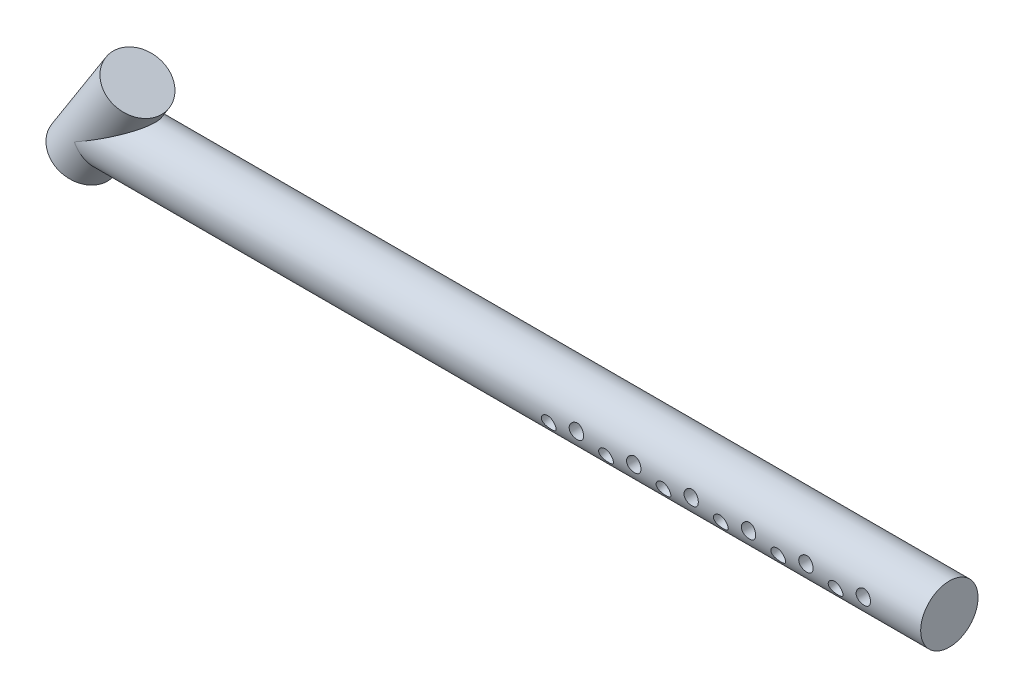
SolidWorks part; units mm, degrees
ref_plane "Front Plane" through (0, 0, 0) normal (0, 0, 1) x (1, 0, 0)
ref_plane "Top Plane" through (0, 0, 0) normal (0, 1, 0) x (1, 0, 0)
ref_plane "Right Plane" through (0, 0, 0) normal (1, 0, 0) x (0, 0, -1)
sketch "Sketch1" plane through (0, 0, 0) normal (0, 0, 1) x (1, 0, 0)
  line L0 (0, 0) -> (-374.65, 0)
  line L1 (211.1174, 0) -> (-211.1174, 0) construction
  line L2 (-359.3649, 23.9928) -> (-383.2479, -13.4959)
  point P7 (-25.4, 0)
  point P8 (-38.1, 0)
  dimension "D1" = 122.5
  dimension "D2" = 44.45
  dimension "D3" = 374.65
  dimension "D4" = 25.4
  dimension "D5" = 12.7
  dimension "D6" = 28.448
sweep "Sweep1" add path "Sketch1" circular profile diameter 25.4 parameters "D3"=25.4
sweep "Sweep2" add path "Sketch1<3>" circular profile diameter 25.4 parameters "D3"=25.4
sketch "Sketch1<3>" plane through (0, 0, 0) normal (0, 0, 1) x (1, 0, 0) same geometry as "Sketch1"
sketch "Sketch18" plane through (0, 0, 0) normal (0, 0, 1) x (1, 0, 0)
  circle A0 centre (-25.4, 0) radius 3.175
  dimension "D1" = 6.35
extrude "Cut-Extrude1" cut sketch "Sketch18" against normal through all both and the other way through all
ref_plane "Plane1" through (0, 0, 0) normal (0, -0.2588, 0.9659) x (-1, 0, 0)
sketch "Sketch23" plane through (0, 0, 0) normal (0, -0.2588, 0.9659) x (-1, 0, 0)
  circle A0 centre (38.1, 0) radius 3.175
  dimension "D1" = 6.35
extrude "Cut-Extrude2" cut sketch "Sketch23" against normal through all both and the other way through all
pattern_linear "LPattern1" count 6 spacing 25.4 along (-1, 0, 0) of "Cut-Extrude2", "Cut-Extrude1"
equation "\"bar_dia\"= 1in"
equation "\"D3@Sweep2\"=\"bar_dia\""
equation "\"hole_dia\"= 0.25in"
equation "\"D1@Sketch18\"=\"hole_dia\""
equation "\"D1@Sketch23\"=\"hole_dia\""
